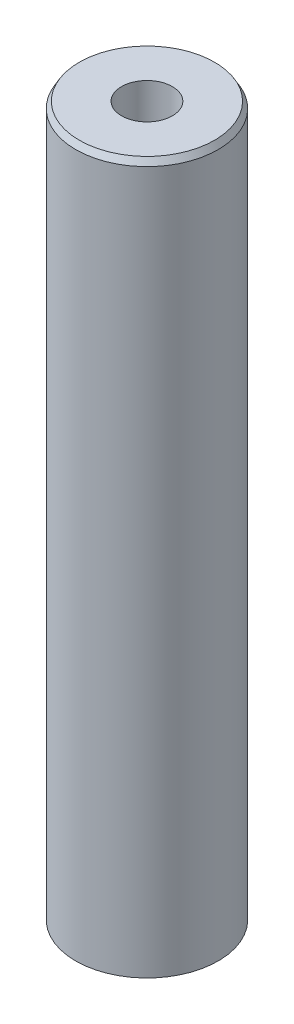
SolidWorks part; units mm, degrees
ref_plane "Front Plane" through (0, 0, 0) normal (0, 0, 1) x (1, 0, 0)
ref_plane "Top Plane" through (0, 0, 0) normal (0, 1, 0) x (1, 0, 0)
ref_plane "Right Plane" through (0, 0, 0) normal (1, 0, 0) x (0, 0, -1)
sketch "Sketch1" plane through (0, 0, 0) normal (0, 1, 0) x (1, 0, 0)
  circle A0 centre (0, 0) radius 60
  dimension "SHAFT_OD" = 120
extrude "Boss-Extrude1" add sketch "Sketch1" along normal blind 600
sketch "Sketch2" plane through (0, 0, 0) normal (0, 1, 0) x (1, 0, 0)
  circle A0 centre (0, 0) radius 21.3816
  dimension "BORE_D" = 42.7632
extrude "Cut-Extrude1" cut sketch "Sketch2" along normal through all
chamfer "Chamfer1" distance 5.2907 angle 30 2 edges at (0, 600, 60) (0, 0, 60) first distance on face at (0, 600, 60) first distance on face at (0, 0, 21.3816)
